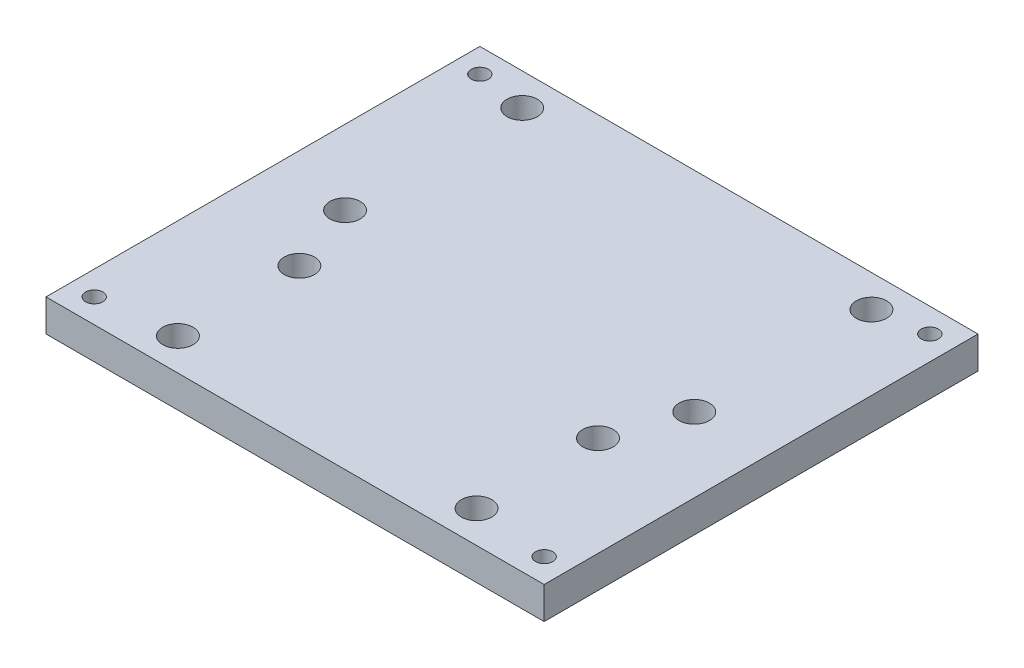
SolidWorks part; units mm, degrees
material "Polyurethane Foam Rigid"
ref_plane "Front Plane" through (0, 0, 0) normal (0, 0, 1) x (1, 0, 0)
ref_plane "Top Plane" through (0, 0, 0) normal (0, 1, 0) x (1, 0, 0)
ref_plane "Right Plane" through (0, 0, 0) normal (1, 0, 0) x (0, 0, -1)
sketch "Sketch1" plane through (0, 0, 0) normal (0, 1, 0) x (1, 0, 0)
  line L0 (-49.2125, 42.8625) -> (49.2125, 42.8625)
  line L1 (-44.45, -38.1) -> (44.45, -38.1) construction
  line L2 (-44.45, -38.1) -> (-44.45, 38.1) construction
  line L3 (-44.45, 38.1) -> (44.45, 38.1) construction
  line L4 (44.45, -38.1) -> (44.45, 38.1) construction
  line L5 (-44.45, -38.1) -> (44.45, 38.1) construction
  line L6 (-44.45, 38.1) -> (44.45, -38.1) construction
  line L7 (49.2125, -42.8625) -> (49.2125, 42.8625)
  line L8 (-49.2125, -42.8625) -> (49.2125, -42.8625)
  line L9 (-49.2125, -42.8625) -> (-49.2125, 42.8625)
  point P0 (0, 0)
  dimension "D1" = 88.9
  dimension "D2" = 76.2
  dimension "D3" = 4.7625
extrude "Boss-Extrude1" add sketch "Sketch1" along normal blind 6.35
hole_wizard "M3 Clearance Hole1" positions "3DSketch1" profile "Sketch2" hole size "M3" standard "ANSI Metric" end condition through all
sketch3d "3DSketch1"
  point P0 (-44.45, 0, 38.1)
  point P3 (44.45, 0, 38.1)
  point P6 (-44.45, 0, -38.1)
  point P9 (44.45, 0, -38.1)
sketch "Sketch2" plane through (-44.45, 0, 38.1) normal (1, 0, 0) x (0, 0, -1)
  line L0 (0, 0) -> (0, 6.35)
  line L1 (0, 6.35) -> (1.7, 6.35)
  line L2 (1.7, 6.35) -> (1.7, 0)
  line L5 (1.7, 0) -> (0, 0)
  line L11 (0, -6.35) -> (0, 107.95) construction
  dimension "Thru Hole Dia." = 3.4
  dimension "Thru Hole Depth" = 6.35
sketch "Sketch3" plane through (0, 6.35, 0) normal (0, 1, 0) x (1, 0, 0)
  line L0 (0, 19.0125) -> (0, -24.5125) construction
  line L1 (49.2125, 42.8625) -> (-49.2125, 42.8625) construction
  line L2 (-34.5, 1.5125) -> (34.5, 1.5125) construction
  line L3 (-34.5, 1.5125) -> (-34.5, 36.5125) construction
  line L4 (-34.5, 36.5125) -> (34.5, 36.5125) construction
  line L5 (34.5, 1.5125) -> (34.5, 36.5125) construction
  line L6 (-34.5, 1.5125) -> (34.5, 36.5125) construction
  line L7 (-34.5, 36.5125) -> (34.5, 1.5125) construction
  line L8 (-29.5, -12.5125) -> (29.5, -12.5125) construction
  line L9 (-29.5, -12.5125) -> (-29.5, -36.5125) construction
  line L10 (-29.5, -36.5125) -> (29.5, -36.5125) construction
  line L11 (29.5, -12.5125) -> (29.5, -36.5125) construction
  line L12 (-29.5, -12.5125) -> (29.5, -36.5125) construction
  line L13 (-29.5, -36.5125) -> (29.5, -12.5125) construction
  line L14 (-49.2125, -42.8625) -> (49.2125, -42.8625) construction
  circle A0 centre (-34.5, 36.5125) radius 3
  circle A1 centre (34.5, 36.5125) radius 3
  circle A2 centre (34.5, 1.5125) radius 3
  circle A3 centre (-34.5, 1.5125) radius 3
  circle A4 centre (-29.5, -12.5125) radius 3
  circle A5 centre (-29.5, -36.5125) radius 3
  circle A6 centre (29.5, -36.5125) radius 3
  circle A7 centre (29.5, -12.5125) radius 3
  dimension "D1" = 6
  dimension "D2" = 69
  dimension "D3" = 59
  dimension "D4" = 6.35
  dimension "D5" = 6.35
  dimension "D6" = 24
  dimension "D7" = 35
extrude "Cut-Extrude1" cut sketch "Sketch3" against normal through all
equation "\"D5@Sketch3\"=\"D4@Sketch3\""
